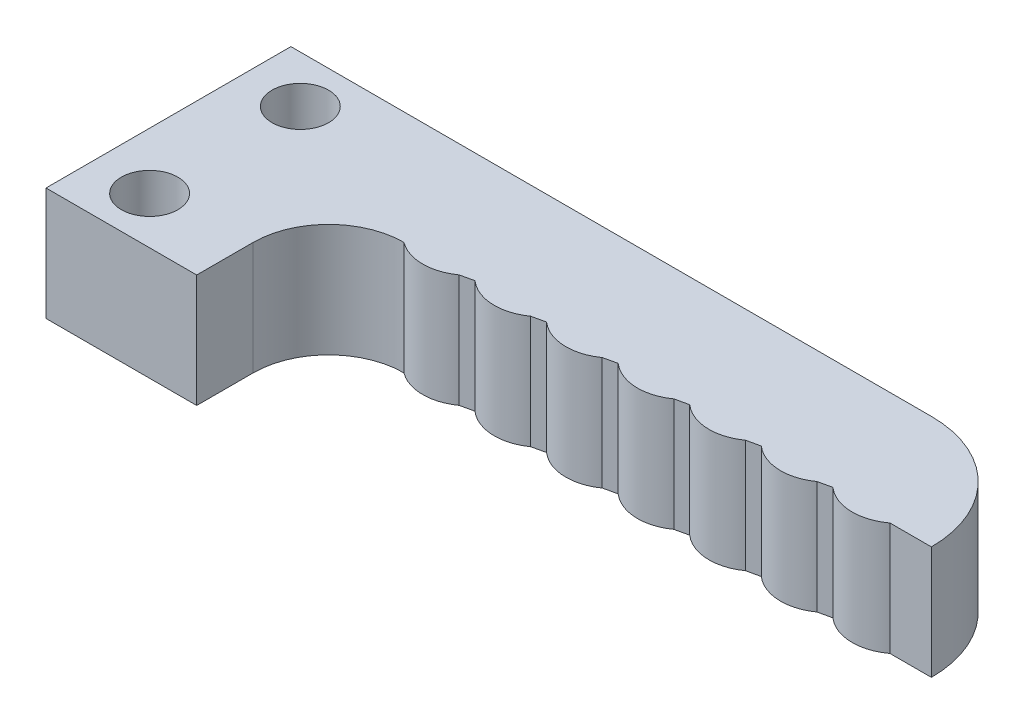
SolidWorks part; units mm, degrees
ref_plane "Front Plane" through (0, 0, 0) normal (0, 0, 1) x (1, 0, 0)
ref_plane "Top Plane" through (0, 0, 0) normal (0, 1, 0) x (1, 0, 0)
ref_plane "Right Plane" through (0, 0, 0) normal (1, 0, 0) x (0, 0, -1)
ref_plane "Plane1" through (0, 0, 0) normal (0, -1, 0) x (1, 0, 0)
sketch "Sketch1" plane through (0, 0, 0) normal (0, -1, 0) x (1, 0, 0)
  line L0 (20, -0.5) -> (17.8, -0.5)
  line L1 (-12, 3.5) -> (-12, 6.5)
  line L2 (-12, 6.5) -> (-20, 6.5)
  line L3 (-20, 6.5) -> (-20, -6.5)
  line L4 (-20, -6.5) -> (14, -6.5)
  arc A0 (14, -6.5) -> (20, -0.5) centre (14, -0.5) ccw
  arc A1 (17.8, -0.5) -> (14.4, -0.8752) centre (16.3, -2.5) ccw
  arc A2 (14.4, -0.8752) -> (10.6, -0.8752) centre (12.5, -2.5) ccw
  arc A3 (10.6, -0.8752) -> (6.8, -0.8752) centre (8.7, -2.5) ccw
  arc A4 (6.8, -0.8752) -> (3, -0.8752) centre (4.9, -2.5) ccw
  arc A5 (3, -0.8752) -> (-0.8, -0.8752) centre (1.1, -2.5) ccw
  arc A6 (-0.8, -0.8752) -> (-4.6, -0.8752) centre (-2.7, -2.5) ccw
  arc A7 (-4.6, -0.8752) -> (-8, -0.5) centre (-6.5, -2.5) ccw
  arc A8 (-8, -0.5) -> (-12, 3.5) centre (-8, 3.5) cw
extrude "Boss-Extrude1" add sketch "Sketch1" against normal blind 6
chamfer "Chamfer1" distance 0.5 angle 36.87 6 edges at (14.4, 3, -0.8752) (3, 3, -0.8752) (-4.6, 3, -0.8752) (10.6, 3, -0.8752) (6.8, 3, -0.8752) (-0.8, 3, -0.8752) first distance on face at (12.5, 3, -0.4376) first distance on face at (1.1, 3, -0.4376) first distance on face at (-6.2629, 3, -0.3513) first distance on face at (8.7, 3, -0.4376) first distance on face at (4.9, 3, -0.4376) first distance on face at (-2.7, 3, -0.4376)
sketch "Sketch2" plane through (0, 6, 0) normal (0, 1, 0) x (1, 0, 0)
  line L0 (-17, 6.5) -> (-17, -6.5) construction
  line L1 (-20, 6.5) -> (14, 6.5) construction
  line L2 (-12, -6.5) -> (-20, -6.5) construction
  line L3 (-20, -6.5) -> (-20, 6.5) construction
  circle A0 centre (-17, 4) radius 1.5
  circle A1 centre (-17, -4) radius 1.5
  point P10 (0, 0)
  point P11 (0, 0)
  dimension "D1" = 3
  dimension "D2" = 3
  dimension "D3" = 2.5
  dimension "D4" = 3
  dimension "D5" = 2.5
extrude "Cut-Extrude1" cut sketch "Sketch2" against normal through all
